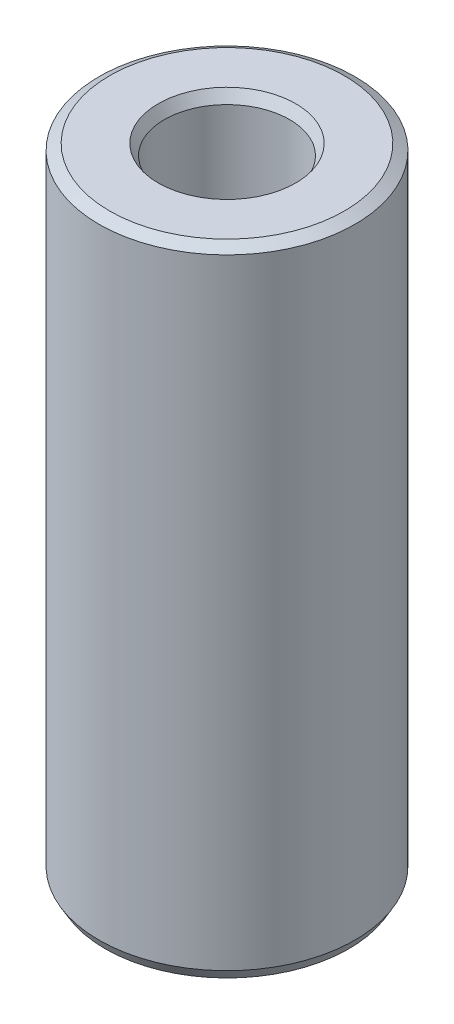
SolidWorks part; units mm, degrees
ref_plane "Front Plane" through (0, 0, 0) normal (0, 0, 1) x (1, 0, 0)
ref_plane "Top Plane" through (0, 0, 0) normal (0, 1, 0) x (1, 0, 0)
ref_plane "Right Plane" through (0, 0, 0) normal (1, 0, 0) x (0, 0, -1)
sketch "Sketch1" plane through (0, 0, 0) normal (0, 1, 0) x (1, 0, 0)
  circle A0 centre (0, 0) radius 5
  dimension "SLEEVE_OD" = 10
extrude "Boss-Extrude1" add sketch "Sketch1" along normal blind 24.8776
sketch "Sketch2" plane through (0, 0, 0) normal (0, 1, 0) x (1, 0, 0)
  circle A0 centre (0, 0) radius 2.4459
  dimension "BORE_D" = 4.8918
extrude "Cut-Extrude1" cut sketch "Sketch2" along normal through all
chamfer "Chamfer1" distance 0.2405 angle 60 4 edges at (0, 24.8776, 2.4459) (0, 0, 2.4459) (0, 0, 5) (0, 24.8776, 5) first distance on face at (0, 24.8776, 2.4459) first distance on face at (0, 0, 2.4459) first distance on face at (0, 24.8776, 5)
